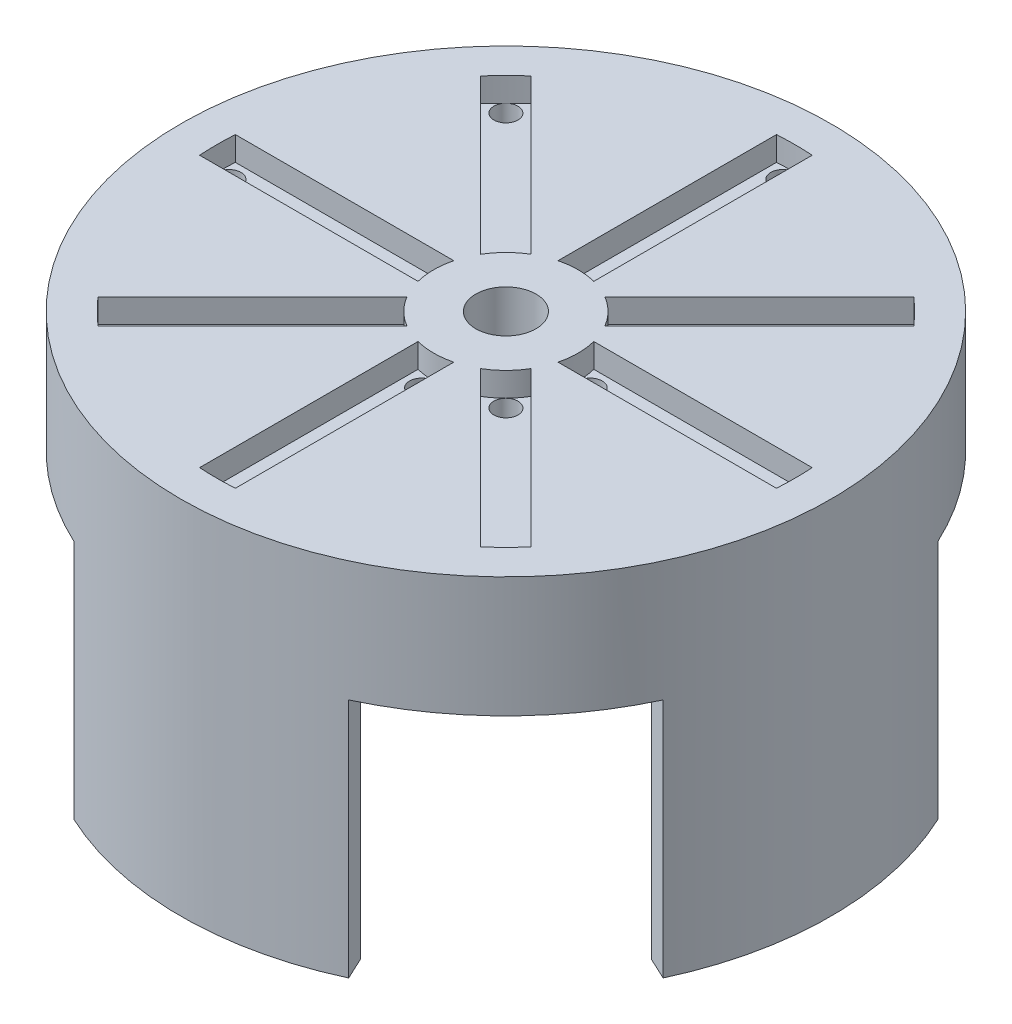
SolidWorks part; units mm, degrees
ref_plane "Спереди" through (0, 0, 0) normal (0, 0, 1) x (1, 0, 0)
ref_plane "Сверху" through (0, 0, 0) normal (0, 1, 0) x (1, 0, 0)
ref_plane "Справа" through (0, 0, 0) normal (1, 0, 0) x (0, 0, -1)
sketch "Эскиз1" plane through (0, 0, 0) normal (0, 1, 0) x (1, 0, 0)
  circle A0 centre (0, 0) radius 27
extrude "Бобышка-Вытянуть1" add sketch "Эскиз1" along normal blind 10
sketch "Эскиз2" plane through (0, 10, 0) normal (0, 1, 0) x (1, 0, 0)
  circle A0 centre (0, 0) radius 2.5
extrude "Вырез-Вытянуть1" cut sketch "Эскиз2" against normal blind 15
sketch "Эскиз3" plane through (0, 0, 0) normal (0, -1, 0) x (1, 0, 0)
  line L0 (0, 0) -> (-21130.9131, 45315.3894) construction
  line L1 (0, 0) -> (21130.9131, 45315.3894) construction
  line L2 (-11.4107, 24.4703) -> (-10.5655, 22.6577)
  line L3 (10.5655, 22.6577) -> (11.4107, 24.4703)
  line L4 (24.4703, 11.4107) -> (22.6577, 10.5655)
  line L5 (22.6577, -10.5655) -> (24.4703, -11.4107)
  line L6 (11.4107, -24.4703) -> (10.5655, -22.6577)
  line L7 (-10.5655, -22.6577) -> (-11.4107, -24.4703)
  line L8 (-24.4703, -11.4107) -> (-22.6577, -10.5655)
  line L9 (-22.6577, 10.5655) -> (-24.4703, 11.4107)
  circle A0 centre (0, 0) radius 27 construction
  circle A1 centre (0, 0) radius 25 construction
  arc A2 (-10.5655, 22.6577) -> (10.5655, 22.6577) centre (0, 0) cw
  arc A3 (-11.4107, 24.4703) -> (11.4107, 24.4703) centre (0, 0) cw
  arc A4 (24.4703, 11.4107) -> (24.4703, -11.4107) centre (0, 0) cw
  arc A5 (22.6577, 10.5655) -> (22.6577, -10.5655) centre (0, 0) cw
  arc A6 (11.4107, -24.4703) -> (-11.4107, -24.4703) centre (0, 0) cw
  arc A7 (10.5655, -22.6577) -> (-10.5655, -22.6577) centre (0, 0) cw
  arc A8 (-24.4703, -11.4107) -> (-24.4703, 11.4107) centre (0, 0) cw
  arc A9 (-22.6577, -10.5655) -> (-22.6577, 10.5655) centre (0, 0) cw
  point P29 (0, 0)
  dimension "D1" = 4
extrude "Бобышка-Вытянуть2" add sketch "Эскиз3" along normal blind 20
sketch "Эскиз4" plane through (0, 10, 0) normal (0, 1, 0) x (1, 0, 0)
  line L0 (-1000, 0) -> (49000, 0) construction
  line L1 (0, -1000) -> (0, 49000) construction
  line L2 (-707.1068, -707.1068) -> (34648.2323, 34648.2323) construction
  line L3 (-707.1068, 707.1068) -> (34648.2323, -34648.2323) construction
  line L4 (2.1, -999.0922) -> (2.1, 49000.9078) construction
  line L5 (-2.1, -998.274) -> (-2.1, 49001.726) construction
  line L6 (-1002.1212, 2.1) -> (48997.8788, 2.1) construction
  line L7 (-1001.6667, -2.1) -> (48998.3333, -2.1) construction
  line L8 (-705.0068, -707.1068) -> (34650.3323, 34648.2323) construction
  line L9 (-709.2068, -707.1068) -> (34646.1323, 34648.2323) construction
  line L10 (-709.2068, 707.1068) -> (34646.1323, -34648.2323) construction
  line L11 (-705.0068, 707.1068) -> (34650.3323, -34648.2323) construction
  line L12 (-17.988, 15.888) -> (-5.1607, 3.0607)
  line L13 (-15.888, 17.988) -> (-3.0607, 5.1607)
  line L14 (1.4849, 23.954) -> (1.4849, 5.8133)
  line L15 (-1.4849, 23.954) -> (-1.4849, 5.8133)
  line L16 (17.988, 15.888) -> (5.1607, 3.0607)
  line L17 (15.888, 17.988) -> (3.0607, 5.1607)
  line L18 (23.954, -1.4849) -> (5.8133, -1.4849)
  line L19 (23.954, 1.4849) -> (5.8133, 1.4849)
  line L20 (15.888, -17.988) -> (3.0607, -5.1607)
  line L21 (17.988, -15.888) -> (5.1607, -3.0607)
  line L22 (-1.4849, -23.954) -> (-1.4849, -5.8133)
  line L23 (1.4849, -23.954) -> (1.4849, -5.8133)
  line L24 (-17.988, -15.888) -> (-5.1607, -3.0607)
  line L25 (-15.888, -17.988) -> (-3.0607, -5.1607)
  line L26 (-23.954, 1.4849) -> (-5.8133, 1.4849)
  line L27 (-23.954, -1.4849) -> (-5.8133, -1.4849)
  circle A0 centre (0, 0) radius 15 construction
  circle A1 centre (0, 0) radius 24 construction
  circle A2 centre (0, 0) radius 6 construction
  arc A3 (-17.988, 15.888) -> (-15.888, 17.988) centre (0, 0) cw
  arc A4 (-5.1607, 3.0607) -> (-3.0607, 5.1607) centre (0, 0) cw
  arc A5 (-1.4849, 23.954) -> (1.4849, 23.954) centre (0, 0) cw
  arc A6 (-1.4849, 5.8133) -> (1.4849, 5.8133) centre (0, 0) cw
  arc A7 (15.888, 17.988) -> (17.988, 15.888) centre (0, 0) cw
  arc A8 (3.0607, 5.1607) -> (5.1607, 3.0607) centre (0, 0) cw
  arc A9 (23.954, 1.4849) -> (23.954, -1.4849) centre (0, 0) cw
  arc A10 (5.8133, 1.4849) -> (5.8133, -1.4849) centre (0, 0) cw
  arc A11 (17.988, -15.888) -> (15.888, -17.988) centre (0, 0) cw
  arc A12 (5.1607, -3.0607) -> (3.0607, -5.1607) centre (0, 0) cw
  arc A13 (1.4849, -23.954) -> (-1.4849, -23.954) centre (0, 0) cw
  arc A14 (1.4849, -5.8133) -> (-1.4849, -5.8133) centre (0, 0) cw
  arc A15 (-15.888, -17.988) -> (-17.988, -15.888) centre (0, 0) cw
  arc A16 (-3.0607, -5.1607) -> (-5.1607, -3.0607) centre (0, 0) cw
  arc A17 (-23.954, -1.4849) -> (-23.954, 1.4849) centre (0, 0) cw
  arc A18 (-5.8133, -1.4849) -> (-5.8133, 1.4849) centre (0, 0) cw
  point P67 (0, 0)
  dimension "D1" = 8
extrude "Вырез-Вытянуть2" cut sketch "Эскиз4" against normal blind 2
sketch "Эскиз5" plane through (0, 10, 0) normal (0, 1, 0) x (1, 0, 0)
  circle A0 centre (0, 0) radius 6 construction
  circle A1 centre (0, 0) radius 7 construction
  circle A2 centre (-7, 0) radius 1
  circle A3 centre (0, 0) radius 23 construction
  circle A4 centre (-23, 0) radius 1
  circle A5 centre (-16.2635, 16.2635) radius 1
  circle A6 centre (-4.9497, 4.9497) radius 1
  circle A7 centre (0, 23) radius 1
  circle A8 centre (0, 7) radius 1
  circle A9 centre (16.2635, 16.2635) radius 1
  circle A10 centre (4.9497, 4.9497) radius 1
  circle A11 centre (23, 0) radius 1
  circle A12 centre (7, 0) radius 1
  circle A13 centre (16.2635, -16.2635) radius 1
  circle A14 centre (4.9497, -4.9497) radius 1
  circle A15 centre (0, -23) radius 1
  circle A16 centre (0, -7) radius 1
  circle A17 centre (-16.2635, -16.2635) radius 1
  circle A18 centre (-4.9497, -4.9497) radius 1
  point P40 (0, 0)
  dimension "D1" = 8
extrude "Вырез-Вытянуть3" cut sketch "Эскиз5" against normal blind 37 and the other way blind 37
